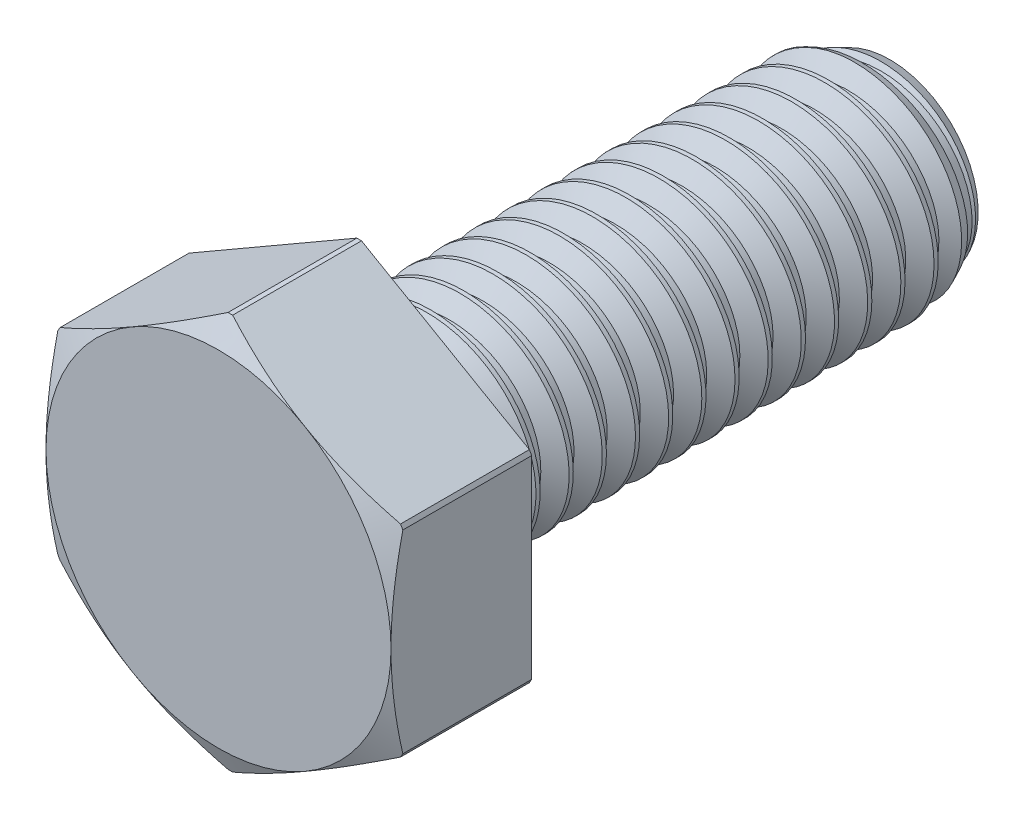
SolidWorks part; units mm, degrees
ref_plane "Front" through (0, 0, 0) normal (0, 0, 1) x (1, 0, 0)
ref_plane "Top" through (0, 0, 0) normal (0, 1, 0) x (1, 0, 0)
ref_plane "Right" through (0, 0, 0) normal (1, 0, 0) x (0, 0, -1)
sketch "Sketch1" plane through (0, 0, 0) normal (1, 0, 0) x (0, 0, -1)
  line L0 (0, 0) -> (-5.3, 0) construction
  line L1 (0, 0) -> (20, 0)
  line L2 (0, 0) -> (0, 4)
  line L3 (0, 4) -> (20, 4)
  line L4 (20, 0) -> (20, 4)
  line L5 (0, -4) -> (20, -4) construction
  point P7 (13.6719, 4)
  point P8 (13.6719, -4)
  dimension "D1" = 20
  dimension "Thread Dia" = 8
  dimension "Length" = 20
  dimension "Head Height" = 5.3
  dimension "Note Dim" = 6.3281
revolve "Revolve1" add sketch "Sketch1" angle 360 about L0
sketch "Sketch6" plane through (0, 0, -20) normal (0, 0, -1) x (-1, 0, 0)
  circle A0 centre (0, 0) radius 4 construction
  circle A1 centre (0, 0) radius 4
curve "Helix/Spiral1" pitch 1.25 height 21.25 radius 4 centre (0, 0, -20) axis (0, 0, 1) start towards (0, 1, 0) parameters "Lenght"=21.25, "Pitch"=1.25
sketch "Sketch2" plane through (0, 0, 0) normal (1, 0, 0) x (0, 0, -1)
  line L1 (19.9219, 4.1353) -> (20.5469, 3.0528) construction
  line L2 (20.5469, 3.0528) -> (21.1719, 4.1353) construction
  line L3 (21.1719, 4.1353) -> (19.9219, 4.1353) construction
  line L4 (20.5469, 4.1353) -> (20.5469, 3.0528) construction
  line L5 (20, 4) -> (21.0938, 4) construction
  line L6 (21.0938, 4) -> (20.7031, 3.3234)
  line L7 (20.7031, 3.3234) -> (20.3906, 3.3234)
  line L8 (21.0938, 4) -> (19.9219, 4.1353)
  line L9 (19.9219, 4.1353) -> (20.3906, 3.3234)
  dimension "D1" = 60
  dimension "Thread Pitch" = 1.25
  dimension "D2" = 0.3125
  dimension "D3" = 1.0938
sweep "Cut-Sweep1" cut profiles "Sketch2" path "Helix/Spiral1"
sketch "Sketch3" plane through (0, 0, 0) normal (1, 0, 0) x (0, 0, -1)
  line L0 (20, 3.3234) -> (18.5491, 4)
  line L1 (18.5491, 4) -> (20, 4)
  line L2 (20, 4) -> (20, 3.3234)
  line L3 (0, 4) -> (20, 4) construction
  line L4 (20, 0) -> (20, 4) construction
  line L5 (18.5491, 0) -> (0, 0) construction
  line L6 (18.5491, 4) -> (18.5491, -4) construction
  line L7 (0, -4) -> (20, -4) construction
  line L8 (20, 2.8284) -> (20, 4) construction
  line L9 (20, 3.3234) -> (20.3906, 3.3234) construction
  dimension "D1" = 25
  dimension "D2" = 8
revolve "Cut-Revolve2" cut sketch "Sketch3" angle 360 about L5
sketch "Sketch4" plane through (0, 0, 0) normal (0, 0, 1) x (1, 0, 0)
  line L1 (0, 7.5056) -> (-6.5, 3.7528)
  line L2 (-6.5, 3.7528) -> (-6.5, -3.7528)
  line L3 (-6.5, -3.7528) -> (0, -7.5056)
  line L4 (0, -7.5056) -> (6.5, -3.7528)
  line L5 (6.5, -3.7528) -> (6.5, 3.7528)
  line L6 (6.5, 3.7528) -> (0, 7.5056)
  circle A0 centre (0, 0) radius 6.5 construction
  circle A1 centre (0, 0) radius 6.5 construction
  dimension "Head Dia" = 13
extrude "Extrude1" add sketch "Sketch4" along normal up to vertex (5.3 mm away) up to point (0, 0, 5.3)
sketch "Sketch5" plane through (0, 0, 0) normal (1, 0, 0) x (0, 0, -1)
  line L0 (-5.3, 6.5) -> (-4.8545, 7.4553)
  line L1 (0, 7.5056) -> (-5.3, 7.5056)
  line L2 (-5.3, 7.5056) -> (-5.3, 6.5)
  line L3 (0, 0) -> (-5.3, 0) construction
  line L4 (-5.3, 7.5056) -> (0, 7.5056) construction
  line L5 (-5.3, 3.7528) -> (-5.3, 7.5056) construction
  line L6 (-4.8545, 7.4553) -> (0, 7.4553)
  line L7 (-5.3, 6.5) -> (0, 6.5) construction
  line L10 (0, 7.4553) -> (0, 7.5056)
  line L11 (0, 3.7528) -> (0, 7.5056) construction
  dimension "D4" = 0.0503
  dimension "D1" = 25
  dimension "D3" = 1.0056
  dimension "D5" = 5.3
  dimension "D6" = 20
revolve "Cut-Revolve3" cut sketch "Sketch5" angle 360 about L3
equation "\"D2@Sketch2\"=\"Thread Pitch@Sketch2\"*1/4"
equation "\"D3@Sketch2\"=\"Thread Pitch@Sketch2\"*7/8"
equation "\"D4@Sketch5\"=\"D3@Sketch5\"/20"
equation "\"Pitch@Helix/Spiral1\" = \"Thread Pitch@Sketch2\""
equation "\"Lenght@Helix/Spiral1\" = \"D1@Sketch1\" + \"Pitch@Helix/Spiral1\""
equation "\"Note Dim@Sketch1\" = \"Thread Pitch@Sketch2\"*5.0625"
